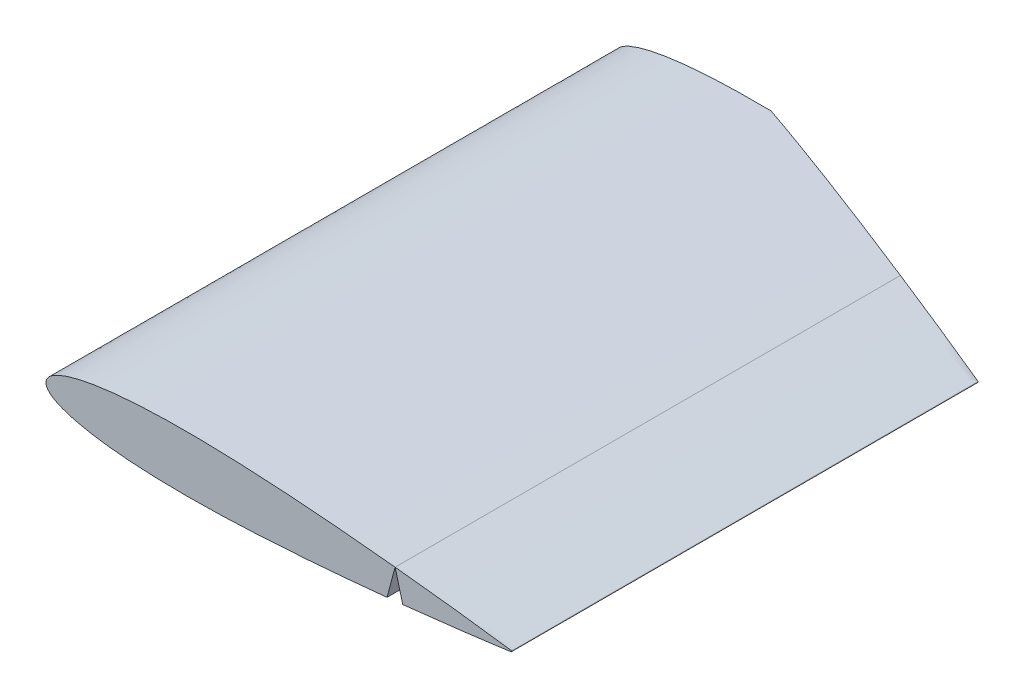
SolidWorks part; units mm, degrees
material "Thornel Mat VMA Foam Core"
ref_plane "Front Plane" through (0, 0, 0) normal (0, 0, 1) x (1, 0, 0)
ref_plane "Top Plane" through (0, 0, 0) normal (0, 1, 0) x (1, 0, 0)
ref_plane "Right Plane" through (0, 0, 0) normal (1, 0, 0) x (0, 0, -1)
curve "Curve1"
  spline degree 3 poles (0.0004, -0.0044, 0) (-0.0002, 0, 0) (0.0004, 0.0044, 0) (0.0023, 0.0087, 0) (0.0053, 0.0128, 0) (0.0094, 0.0167, 0) (0.0147, 0.0206, 0) (0.0211, 0.0243, 0) (0.0286, 0.0279, 0) (0.0372, 0.0313, 0) (0.0468, 0.0347, 0) (0.0576, 0.0378, 0) (0.0693, 0.0408, 0) (0.0821, 0.0436, 0) (0.0958, 0.0462, 0) (0.1104, 0.0486, 0) (0.126, 0.0507, 0) (0.1425, 0.0527, 0) (0.1597, 0.0544, 0) (0.1778, 0.056, 0) (0.1966, 0.0572, 0) (0.2162, 0.0583, 0) (0.2364, 0.0591, 0) (0.2572, 0.0596, 0) (0.2786, 0.06, 0) (0.3005, 0.0601, 0) (0.3228, 0.0599, 0) (0.3456, 0.0596, 0) (0.3688, 0.0591, 0) (0.3922, 0.0583, 0) (0.4159, 0.0574, 0) (0.4398, 0.0563, 0) (0.4638, 0.0551, 0) (0.4879, 0.0537, 0) (0.5121, 0.0522, 0) (0.5362, 0.0505, 0) (0.5602, 0.0488, 0) (0.5841, 0.0469, 0) (0.6078, 0.045, 0) (0.6313, 0.043, 0) (0.6544, 0.0409, 0) (0.6772, 0.0388, 0) (0.6995, 0.0367, 0) (0.7214, 0.0345, 0) (0.7428, 0.0324, 0) (0.7636, 0.0302, 0) (0.7838, 0.028, 0) (0.8033, 0.0259, 0) (0.8222, 0.0238, 0) (0.8402, 0.0217, 0) (0.8575, 0.0196, 0) (0.874, 0.0177, 0) (0.8895, 0.0158, 0) (0.9042, 0.014, 0) (0.9179, 0.0122, 0) (0.9307, 0.0106, 0) (0.9424, 0.0091, 0) (0.9531, 0.0077, 0) (0.9627, 0.0064, 0) (0.9713, 0.0052, 0) (0.9788, 0.0042, 0) (0.9851, 0.0033, 0) (0.9903, 0.0026, 0) (0.9944, 0.002, 0) (0.9973, 0.0017, 0) (0.999, 0.0013, 0) (1.0007, 0.0014, 0) (1.0007, -0.0014, 0) (0.999, -0.0013, 0) (0.9973, -0.0017, 0) (0.9944, -0.002, 0) (0.9903, -0.0026, 0) (0.9851, -0.0033, 0) (0.9788, -0.0042, 0) (0.9713, -0.0052, 0) (0.9627, -0.0064, 0) (0.9531, -0.0077, 0) (0.9424, -0.0091, 0) (0.9307, -0.0106, 0) (0.9179, -0.0122, 0) (0.9042, -0.014, 0) (0.8895, -0.0158, 0) (0.874, -0.0177, 0) (0.8575, -0.0196, 0) (0.8402, -0.0217, 0) (0.8222, -0.0238, 0) (0.8033, -0.0259, 0) (0.7838, -0.028, 0) (0.7636, -0.0302, 0) (0.7428, -0.0324, 0) (0.7214, -0.0345, 0) (0.6995, -0.0367, 0) (0.6772, -0.0388, 0) (0.6544, -0.0409, 0) (0.6313, -0.043, 0) (0.6078, -0.045, 0) (0.5841, -0.0469, 0) (0.5602, -0.0488, 0) (0.5362, -0.0505, 0) (0.5121, -0.0522, 0) (0.4879, -0.0537, 0) (0.4638, -0.0551, 0) (0.4398, -0.0563, 0) (0.4159, -0.0574, 0) (0.3922, -0.0583, 0) (0.3688, -0.0591, 0) (0.3456, -0.0596, 0) (0.3228, -0.0599, 0) (0.3005, -0.0601, 0) (0.2786, -0.06, 0) (0.2572, -0.0596, 0) (0.2364, -0.0591, 0) (0.2162, -0.0583, 0) (0.1966, -0.0572, 0) (0.1778, -0.056, 0) (0.1597, -0.0544, 0) (0.1425, -0.0527, 0) (0.126, -0.0507, 0) (0.1104, -0.0486, 0) (0.0958, -0.0462, 0) (0.0821, -0.0436, 0) (0.0693, -0.0408, 0) (0.0576, -0.0378, 0) (0.0468, -0.0347, 0) (0.0372, -0.0313, 0) (0.0286, -0.0279, 0) (0.0211, -0.0243, 0) (0.0147, -0.0206, 0) (0.0094, -0.0167, 0) (0.0053, -0.0128, 0) (0.0023, -0.0087, 0) (0.0004, -0.0044, 0) (-0.0002, 0, 0) (0.0004, 0.0044, 0) knots -0.006773 -0.004321 -0.002106 0 0.002106 0.004321 0.006773 0.009557 0.012734 0.016343 0.020406 0.024934 0.029933 0.035402 0.041337 0.047732 0.054575 0.061857 0.069565 0.077682 0.086195 0.095084 0.104333 0.113922 0.123829 0.134035 0.144516 0.155249 0.16621 0.177376 0.18872 0.200217 0.21184 0.223563 0.235359 0.2472 0.259058 0.270907 0.282718 0.294465 0.306118 0.317651 0.329037 0.340249 0.35126 0.362045 0.372579 0.382836 0.392793 0.402425 0.411711 0.420628 0.429156 0.437273 0.444962 0.452203 0.458979 0.465275 0.471075 0.476366 0.481134 0.485369 0.48906 0.492198 0.494776 0.496788 0.498228 0.499094 0.499383 0.500617 0.500906 0.501772 0.503212 0.505224 0.507802 0.51094 0.514631 0.518866 0.523634 0.528925 0.534725 0.541021 0.547797 0.555038 0.562727 0.570844 0.579372 0.588289 0.597575 0.607207 0.617164 0.627421 0.637955 0.64874 0.659751 0.670963 0.682349 0.693882 0.705535 0.717282 0.729093 0.740942 0.7528 0.764641 0.776437 0.78816 0.799783 0.81128 0.822624 0.83379 0.844751 0.855484 0.865965 0.876171 0.886078 0.895667 0.904916 0.913805 0.922318 0.930435 0.938143 0.945425 0.952268 0.958663 0.964598 0.970067 0.975066 0.979594 0.983657 0.987266 0.990443 0.993227 0.995679 0.997894 1 1.002106 1.004321 1.006773 periodic
sketch "Sketch1" plane through (0, 0, 0) normal (0, 0, 1) x (1, 0, 0)
  line L0 (228.6, 0) -> (0, 0) construction
  line L1 (0.5505, 0) -> (-0.5505, 0) construction
  line L2 (0, 0) -> (0, 0.0037) construction
  line L3 (0, -0.0661) -> (0, 0.0661) construction
  spline S1 degree 3 poles (0.0941, 1.0023) (-0.0459, 0) (0.0941, -1.0023) (0.5163, -1.979) (1.2063, -2.9191) (2.1555, -3.8265) (3.3611, -4.7045) (4.8212, -5.5539) (6.5336, -6.3738) (8.4955, -7.1622) (10.7028, -7.9169) (13.1508, -8.6353) (15.8342, -9.3147) (18.7469, -9.9527) (21.8822, -10.5465) (25.2329, -11.0942) (28.7913, -11.5933) (32.549, -12.0423) (36.4974, -12.4394) (40.6273, -12.7838) (44.929, -13.0744) (49.3924, -13.3108) (54.0073, -13.4932) (58.7627, -13.6218) (63.6477, -13.6973) (68.6508, -13.7209) (73.7603, -13.694) (78.9643, -13.6184) (84.2506, -13.4961) (89.607, -13.3294) (95.0208, -13.1208) (100.4795, -12.873) (105.9703, -12.5887) (111.4804, -12.2709) (116.997, -11.9225) (122.507, -11.5464) (127.9978, -11.1457) (133.4564, -10.7232) (138.8702, -10.2819) (144.2264, -9.8246) (149.5125, -9.354) (154.7163, -8.873) (159.8255, -8.3842) (164.8283, -7.89) (169.7129, -7.3931) (174.468, -6.8959) (179.0824, -6.4008) (183.5453, -5.9102) (187.8464, -5.4263) (191.9755, -4.9516) (195.9231, -4.4883) (199.6799, -4.0386) (203.2372, -3.6048) (206.5865, -3.1892) (209.7203, -2.7938) (212.631, -2.4208) (215.3118, -2.0722) (217.7567, -1.7502) (219.9598, -1.4564) (221.9158, -1.1925) (223.6207, -0.9608) (225.0694, -0.7609) (226.261, -0.599) (227.1864, -0.4629) (227.8589, -0.3857) (228.2452, -0.3022) (228.6415, -0.3098) (228.6415, 0.3098) (228.2452, 0.3022) (227.8589, 0.3857) (227.1864, 0.4629) (226.261, 0.599) (225.0694, 0.7609) (223.6207, 0.9608) (221.9158, 1.1925) (219.9598, 1.4564) (217.7567, 1.7502) (215.3118, 2.0722) (212.631, 2.4208) (209.7203, 2.7938) (206.5865, 3.1892) (203.2372, 3.6048) (199.6799, 4.0386) (195.9231, 4.4883) (191.9755, 4.9516) (187.8464, 5.4263) (183.5453, 5.9102) (179.0824, 6.4008) (174.468, 6.8959) (169.7129, 7.3931) (164.8283, 7.89) (159.8255, 8.3842) (154.7163, 8.873) (149.5125, 9.354) (144.2264, 9.8246) (138.8702, 10.2819) (133.4564, 10.7232) (127.9978, 11.1457) (122.507, 11.5464) (116.997, 11.9225) (111.4804, 12.2709) (105.9703, 12.5887) (100.4795, 12.873) (95.0208, 13.1208) (89.607, 13.3294) (84.2506, 13.4961) (78.9643, 13.6184) (73.7603, 13.694) (68.6508, 13.7209) (63.6477, 13.6973) (58.7627, 13.6218) (54.0073, 13.4932) (49.3924, 13.3108) (44.929, 13.0744) (40.6273, 12.7838) (36.4974, 12.4394) (32.549, 12.0423) (28.7913, 11.5933) (25.2329, 11.0942) (21.8822, 10.5465) (18.7469, 9.9527) (15.8342, 9.3147) (13.1508, 8.6353) (10.7028, 7.9169) (8.4955, 7.1622) (6.5336, 6.3738) (4.8212, 5.5539) (3.3611, 4.7045) (2.1555, 3.8265) (1.2063, 2.9191) (0.5163, 1.979) (0.0941, 1.0023) (-0.0459, 0) (0.0941, -1.0023) knots -0.006773 -0.004321 -0.002106 0 0.002106 0.004321 0.006773 0.009557 0.012734 0.016343 0.020406 0.024934 0.029933 0.035402 0.041337 0.047732 0.054575 0.061857 0.069565 0.077682 0.086195 0.095084 0.104333 0.113922 0.123829 0.134035 0.144516 0.155249 0.16621 0.177376 0.18872 0.200217 0.21184 0.223563 0.235359 0.2472 0.259058 0.270907 0.282718 0.294465 0.306118 0.317651 0.329037 0.340249 0.35126 0.362045 0.372579 0.382836 0.392793 0.402425 0.411711 0.420628 0.429156 0.437273 0.444962 0.452203 0.458979 0.465275 0.471075 0.476366 0.481134 0.485369 0.48906 0.492198 0.494776 0.496788 0.498228 0.499094 0.499383 0.500617 0.500906 0.501772 0.503212 0.505224 0.507802 0.51094 0.514631 0.518866 0.523634 0.528925 0.534725 0.541021 0.547797 0.555038 0.562727 0.570844 0.579372 0.588289 0.597575 0.607207 0.617164 0.627421 0.637955 0.64874 0.659751 0.670963 0.682349 0.693882 0.705535 0.717282 0.729093 0.740942 0.7528 0.764641 0.776437 0.78816 0.799783 0.81128 0.822624 0.83379 0.844751 0.855484 0.865965 0.876171 0.886078 0.895667 0.904916 0.913805 0.922318 0.930435 0.938143 0.945425 0.952268 0.958663 0.964598 0.970067 0.975066 0.979594 0.983657 0.987266 0.990443 0.993227 0.995679 0.997894 1 1.002106 1.004321 1.006773 only from (0, 0) to (0, 0)
  dimension "D1" = 228.6
extrude "Boss-Extrude1" add sketch "Sketch1" along normal blind 279.908
sketch "Sketch2" plane through (0, 0, 0) normal (0, 0, -1) x (-1, 0, 0)
  line L0 (125.7781, 0) -> (-125.7781, 0) construction
  circle A0 centre (-63.5, 0) radius 6.35
  dimension "D1" = 12.7
  dimension "D2" = 63.5
extrude "Cut-Extrude1" cut sketch "Sketch2" against normal blind 127
sketch "Sketch3" plane through (0, 0, 0) normal (0, 1, 0) x (1, 0, 0)
  line L0 (228.655, 0) -> (228.6, -50.8)
  line L1 (-15.093, 0) -> (15.093, 0) construction
  line L2 (228.6, -279.908) -> (228.6, 0) construction
  line L3 (228.6, -50.8) -> (76.2, 0)
  line L4 (76.2, 0) -> (228.655, 0)
  dimension "D1" = 152.4
  dimension "D2" = 50.8
extrude "Cut-Extrude2" cut sketch "Sketch3" against normal up to next and the other way up to next
sketch "Sketch4" plane through (0, 0, 279.908) normal (0, 0, 1) x (1, 0, 0)
  line L0 (171.45, 0) -> (171.45, 54.9085) construction
  line L1 (129.9152, 0) -> (-129.9152, 0) construction
  line L2 (0, -41.8708) -> (0, 41.8708) construction
  line L3 (171.45, 7.2108) -> (167.4761, -7.6201)
  line L5 (175.2083, -6.8152) -> (171.45, 7.2108)
  arc A0 (175.2083, -6.8152) -> (167.4761, -7.6201) centre (170.3228, 2.5746) cw
  spline S1 degree 3 poles (0.0941, 1.0023) (-0.0459, 0) (0.0941, -1.0023) (0.5163, -1.979) (1.2063, -2.9191) (2.1555, -3.8265) (3.3611, -4.7045) (4.8212, -5.5539) (6.5336, -6.3738) (8.4955, -7.1622) (10.7028, -7.9169) (13.1508, -8.6353) (15.8342, -9.3147) (18.7469, -9.9527) (21.8822, -10.5465) (25.2329, -11.0942) (28.7913, -11.5933) (32.549, -12.0423) (36.4974, -12.4394) (40.6273, -12.7838) (44.929, -13.0744) (49.3924, -13.3108) (54.0073, -13.4932) (58.7627, -13.6218) (63.6477, -13.6973) (68.6508, -13.7209) (73.7603, -13.694) (78.9643, -13.6184) (84.2506, -13.4961) (89.607, -13.3294) (95.0208, -13.1208) (100.4795, -12.873) (105.9703, -12.5887) (111.4804, -12.2709) (116.997, -11.9225) (122.507, -11.5464) (127.9978, -11.1457) (133.4564, -10.7232) (138.8702, -10.2819) (144.2264, -9.8246) (149.5125, -9.354) (154.7163, -8.873) (159.8255, -8.3842) (164.8283, -7.89) (169.7129, -7.3931) (174.468, -6.8959) (179.0824, -6.4008) (183.5453, -5.9102) (187.8464, -5.4263) (191.9755, -4.9516) (195.9231, -4.4883) (199.6799, -4.0386) (203.2372, -3.6048) (206.5865, -3.1892) (209.7203, -2.7938) (212.631, -2.4208) (215.3118, -2.0722) (217.7567, -1.7502) (219.9598, -1.4564) (221.9158, -1.1925) (223.6207, -0.9608) (225.0694, -0.7609) (226.261, -0.599) (227.1864, -0.4629) (227.8589, -0.3857) (228.2452, -0.3022) (228.6415, -0.3098) (228.6415, 0.3098) (228.2452, 0.3022) (227.8589, 0.3857) (227.1864, 0.4629) (226.261, 0.599) (225.0694, 0.7609) (223.6207, 0.9608) (221.9158, 1.1925) (219.9598, 1.4564) (217.7567, 1.7502) (215.3118, 2.0722) (212.631, 2.4208) (209.7203, 2.7938) (206.5865, 3.1892) (203.2372, 3.6048) (199.6799, 4.0386) (195.9231, 4.4883) (191.9755, 4.9516) (187.8464, 5.4263) (183.5453, 5.9102) (179.0824, 6.4008) (174.468, 6.8959) (169.7129, 7.3931) (164.8283, 7.89) (159.8255, 8.3842) (154.7163, 8.873) (149.5125, 9.354) (144.2264, 9.8246) (138.8702, 10.2819) (133.4564, 10.7232) (127.9978, 11.1457) (122.507, 11.5464) (116.997, 11.9225) (111.4804, 12.2709) (105.9703, 12.5887) (100.4795, 12.873) (95.0208, 13.1208) (89.607, 13.3294) (84.2506, 13.4961) (78.9643, 13.6184) (73.7603, 13.694) (68.6508, 13.7209) (63.6477, 13.6973) (58.7627, 13.6218) (54.0073, 13.4932) (49.3924, 13.3108) (44.929, 13.0744) (40.6273, 12.7838) (36.4974, 12.4394) (32.549, 12.0423) (28.7913, 11.5933) (25.2329, 11.0942) (21.8822, 10.5465) (18.7469, 9.9527) (15.8342, 9.3147) (13.1508, 8.6353) (10.7028, 7.9169) (8.4955, 7.1622) (6.5336, 6.3738) (4.8212, 5.5539) (3.3611, 4.7045) (2.1555, 3.8265) (1.2063, 2.9191) (0.5163, 1.979) (0.0941, 1.0023) (-0.0459, 0) (0.0941, -1.0023) knots -0.006773 -0.004321 -0.002106 0 0.002106 0.004321 0.006773 0.009557 0.012734 0.016343 0.020406 0.024934 0.029933 0.035402 0.041337 0.047732 0.054575 0.061857 0.069565 0.077682 0.086195 0.095084 0.104333 0.113922 0.123829 0.134035 0.144516 0.155249 0.16621 0.177376 0.18872 0.200217 0.21184 0.223563 0.235359 0.2472 0.259058 0.270907 0.282718 0.294465 0.306118 0.317651 0.329037 0.340249 0.35126 0.362045 0.372579 0.382836 0.392793 0.402425 0.411711 0.420628 0.429156 0.437273 0.444962 0.452203 0.458979 0.465275 0.471075 0.476366 0.481134 0.485369 0.48906 0.492198 0.494776 0.496788 0.498228 0.499094 0.499383 0.500617 0.500906 0.501772 0.503212 0.505224 0.507802 0.51094 0.514631 0.518866 0.523634 0.528925 0.534725 0.541021 0.547797 0.555038 0.562727 0.570844 0.579372 0.588289 0.597575 0.607207 0.617164 0.627421 0.637955 0.64874 0.659751 0.670963 0.682349 0.693882 0.705535 0.717282 0.729093 0.740942 0.7528 0.764641 0.776437 0.78816 0.799783 0.81128 0.822624 0.83379 0.844751 0.855484 0.865965 0.876171 0.886078 0.895667 0.904916 0.913805 0.922318 0.930435 0.938143 0.945425 0.952268 0.958663 0.964598 0.970067 0.975066 0.979594 0.983657 0.987266 0.990443 0.993227 0.995679 0.997894 1 1.002106 1.004321 1.006773 only from (0, 0) to (0, 0) construction
  dimension "D1" = 171.45
  dimension "D3" = 15
  dimension "D4" = 15
extrude "Cut-Extrude4" cut sketch "Sketch4" against normal up to next
